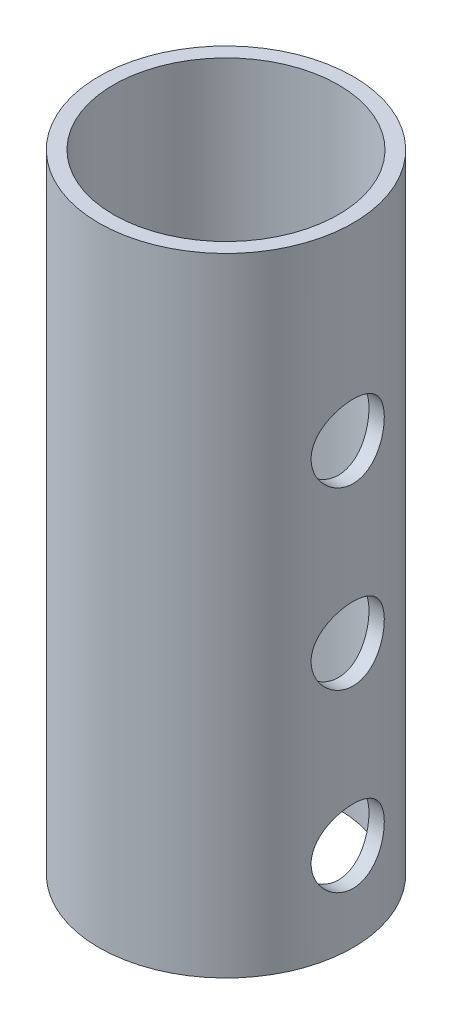
SolidWorks part; units mm, degrees
material "PTFE (general)"
ref_plane "Front Plane" through (0, 0, 0) normal (0, 0, 1) x (1, 0, 0)
ref_plane "Top Plane" through (0, 0, 0) normal (0, 1, 0) x (1, 0, 0)
ref_plane "Right Plane" through (0, 0, 0) normal (1, 0, 0) x (0, 0, -1)
sketch "Sketch1" plane through (0, 0, 0) normal (0, 1, 0) x (1, 0, 0)
  circle A0 centre (0, 0) radius 43.5
  circle A1 centre (0, 0) radius 38.5
  dimension "D1" = 87
  dimension "D2" = 77
extrude "Boss-Extrude1" add sketch "Sketch1" along normal blind 214.8
sketch "Sketch2" plane through (0, 0, 0) normal (1, 0, 0) x (0, 0, -1)
  line L0 (38.5, 214.8) -> (-38.5, 214.8) construction
  circle A0 centre (0, 150.1) radius 12.53
  circle A1 centre (0, 90.1) radius 12.53
  circle A2 centre (0, 30.1) radius 12.53
  dimension "D2" = 25.06
  dimension "D3" = 25.06
  dimension "D4" = 25.06
  dimension "D1" = 64.7
  dimension "D5" = 60
  dimension "D6" = 60
extrude "Cut-Extrude1" cut sketch "Sketch2" along normal through all
sketch "Sketch4" plane through (0, 0, 0) normal (1, 0, 0) x (0, 0, -1)
  circle A0 centre (0, 64.6) radius 7.5
  circle A4 centre (0, 90.1) radius 12.53 construction
  dimension "D1" = 15
  dimension "D3" = 25.5
extrude "Cut-Extrude2" cut sketch "Sketch4" against normal through all
